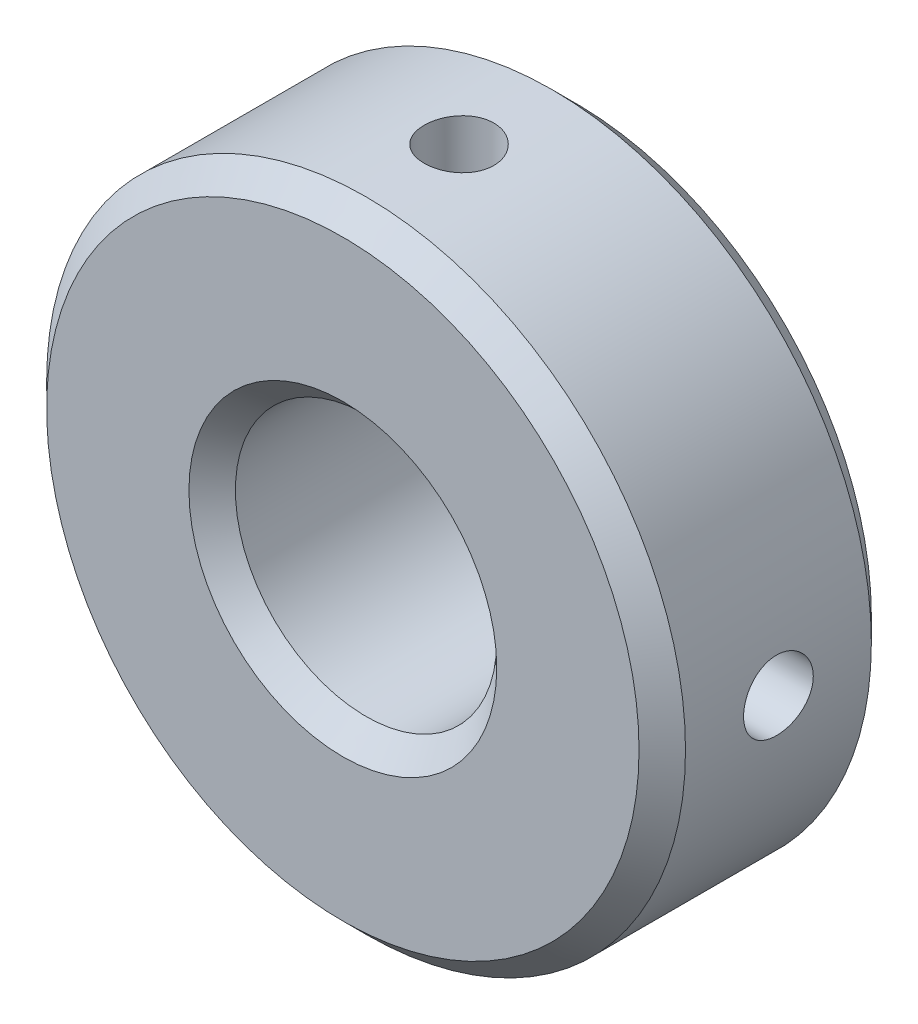
SolidWorks part; units mm, degrees
ref_plane "Front" through (0, 0, 0) normal (0, 0, 1) x (1, 0, 0)
ref_plane "Top" through (0, 0, 0) normal (0, 1, 0) x (1, 0, 0)
ref_plane "Right" through (0, 0, 0) normal (1, 0, 0) x (0, 0, -1)
sketch "Sketch1" plane through (0, 0, 0) normal (0, 0, 1) x (1, 0, 0)
  circle A0 centre (0, 0) radius 11
  circle A1 centre (0, 0) radius 4.5
  dimension "D2" = 9
extrude "BaseNut" add sketch "Sketch1" against normal mid plane 8
cosmetic thread "ThreadCosmetic1" [suppressed] parameters "D2"=10
ref_plane "Plane1" through (0, 11, 0) normal (0, 1, 0) x (-1, 0, 0)
sketch "Sketch2" plane through (0, 0, 0) normal (0, 0, 1) x (1, 0, 0)
  line L0 (0, 14.609) -> (0, -14.0536) construction
  line L2 (0, 11) -> (1.2001, 11)
  line L5 (1.2001, 11) -> (1.2001, 7.6105)
  line L6 (0, 6.9177) -> (1.2001, 7.6105)
  line L7 (0, 11) -> (0, 6.9177)
  circle A1 centre (0, 0) radius 11 construction
  dimension "t" = 3.3895
  dimension "d1" = 2.4002
  dimension "D2" = 60
revolve "Cut-Revolve2" cut sketch "Sketch2" angle 360 about L0
pattern_circular "CirPattern1" count 4 over 360 about axis through (0, 0, -4) along (0, 0, 1) of "Cut-Revolve2"
chamfer "Chamfer1" distance 0.8 angle 45 4 edges at (4.5, 0, -4) (11, 0, -4) (4.5, 0, 4) (11, 0, 4)
sketch "Sketch3" plane through (0, 0, 0) normal (0, 1, 0) x (1, 0, 0)
  line L0 (0, 7.0838) -> (0, -7.8506) construction
  line L1 (4, 3.45) -> (4.5, 3.45)
  line L2 (4.5, 3.45) -> (4.933, 3.2)
  line L3 (4.933, 3.2) -> (4.5, 2.95)
  line L4 (4.5, 2.95) -> (4, 2.95)
  line L5 (4, 2.95) -> (4, 3.45)
  line L6 (4.5, 3.2) -> (-4.5, 3.2) construction
  dimension "D1" = 0.5
  dimension "D2" = 9
revolve "Cut-Revolve10" [suppressed] cut sketch "Sketch3" angle 360 about L0
pattern_linear "LPattern10" [suppressed] count 13 spacing 0.6 along (0, 0, 1) of bodies 106
equation "\"D2@Sketch3\" = \"D2@Sketch1\""
equation "\"D1@Sketch3\" = (  \"D2@ThreadCosmetic1\" - \"D2@Sketch1\" )  / 2"
equation "\"D3@LPattern10\" = \"D1@Sketch3\" * 1.2"
equation "\"D1@LPattern10\" = \"m@BaseNut\" / \"D3@LPattern10\""
